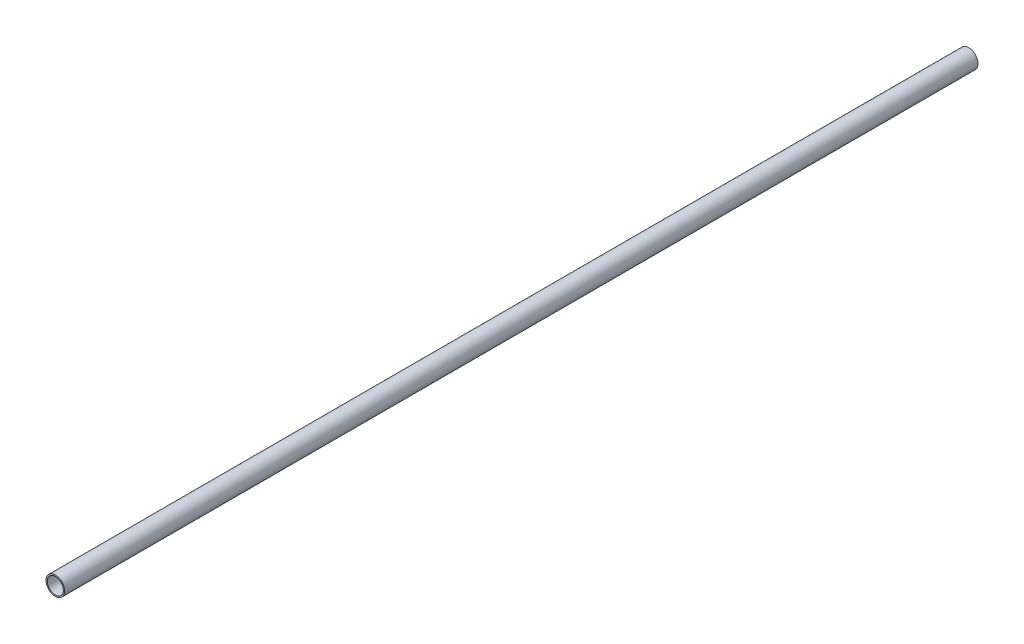
SolidWorks part; units mm, degrees
ref_plane "Front Plane" through (0, 0, 0) normal (0, 0, 1) x (1, 0, 0)
ref_plane "Top Plane" through (0, 0, 0) normal (0, 1, 0) x (1, 0, 0)
ref_plane "Right Plane" through (0, 0, 0) normal (1, 0, 0) x (0, 0, -1)
sketch "Sketch2" plane through (-549.704, -1576.7433, 0) normal (0, 0, -1) x (0.7833, -0.6217, 0)
  circle A6 centre (-549.704, -1576.7433) radius 4.7625
  circle A7 centre (-549.704, -1576.7433) radius 5.5245
  dimension "D1" = 9.525
  dimension "D2" = 11.049
extrude "Boss-Extrude1" add sketch "Sketch2" along normal blind 542.8896
